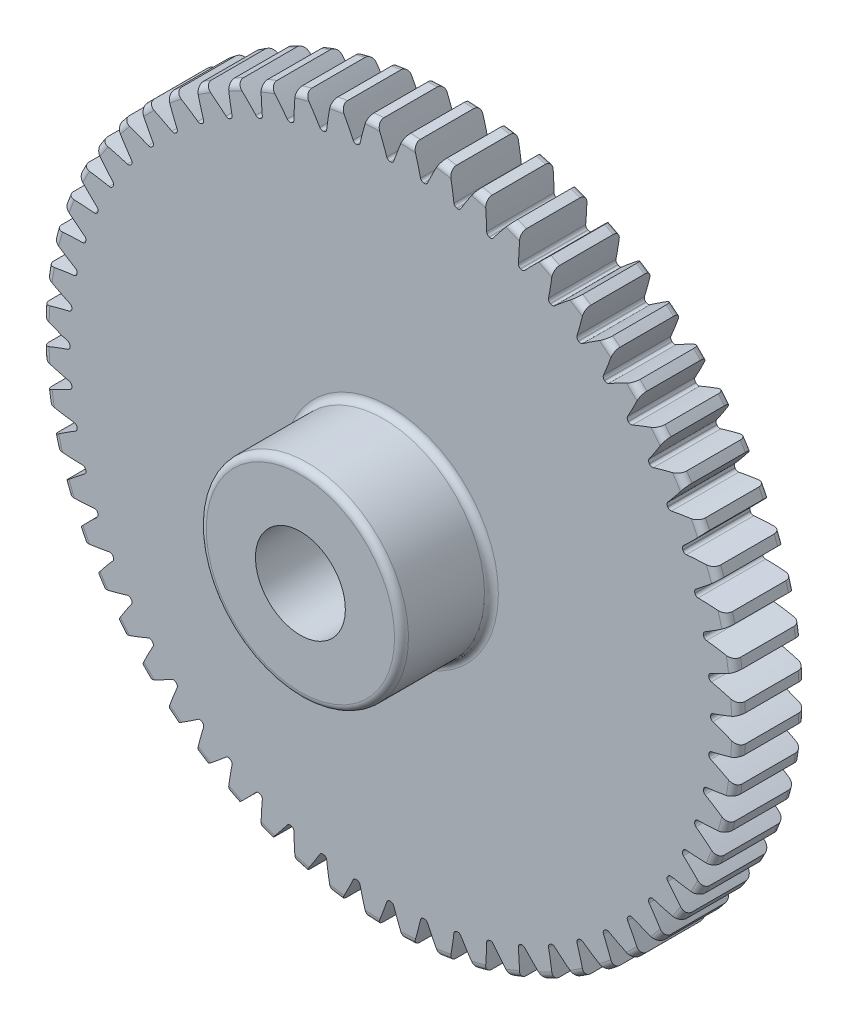
SolidWorks part; units mm, degrees
ref_plane "Front Plane" through (0, 0, 0) normal (0, 0, 1) x (1, 0, 0)
ref_plane "Top Plane" through (0, 0, 0) normal (0, 1, 0) x (1, 0, 0)
ref_plane "Right Plane" through (0, 0, 0) normal (1, 0, 0) x (0, 0, -1)
sketch "Sketch1" plane through (0, 0, 0) normal (0, 0, 1) x (1, 0, 0)
  line L0 (-762, 0) -> (762, 0) construction
  circle A0 centre (0, 0) radius 31 construction
  circle A1 centre (0, 0) radius 30 construction
  circle A2 centre (0, 0) radius 28.5 construction
  circle A3 centre (0, 0) radius 9 construction
  circle A4 centre (0, 0) radius 4 construction
  dimension "D2" = 1
  dimension "D3" = 2.5
  dimension "D1" = 2.5
sketch "Sketch2" plane through (0, 0, 0) normal (1, 0, 0) x (0, 0, -1)
  line L0 (0, 0) -> (-6, 0) construction
  line L1 (-6, 0) -> (-14, 0) construction
  dimension "Overall Width" = 14
  dimension "Face Width" = 6
sketch "Sketch4" plane through (0, 0, 0) normal (1, 0, 0) x (0, 0, -1)
  line L0 (-14, 4) -> (-14, 9)
  line L1 (-14, 9) -> (-6, 9)
  line L2 (-6, 9) -> (-6, 31)
  line L3 (-6, 31) -> (0, 31)
  line L4 (0, 31) -> (0, 4)
  line L5 (-6, 9) -> (-6, 0) construction
  line L6 (0, 31) -> (0, -31) construction
  line L7 (-6, 9) -> (0, 9) construction
  line L12 (-14, 4) -> (0, 4)
revolve "Revolve1" add sketch "Sketch4" angle 360 about L1
fillet "Fillet2" radius 0.62 4 edges at (0, 9, 14) (0, 9, 6) (0, 31, 6) (0, 31, 0)
sketch "Sketch7" plane through (0, 0, 6) normal (0, 0, 1) x (1, 0, 0)
  line L0 (0, 0) -> (0, 31) construction
  line L1 (0.7853, 29.9897) -> (1.1745, 30.9777) construction
  line L3 (1.6224, 30.9575) -> (1.5701, 29.9589) construction
  line L4 (1.5701, 29.9589) -> (1.4916, 28.4609) construction
  line L5 (0, 0) -> (1.4916, 28.4609) construction
  line L6 (0.7853, 29.9897) -> (0, 0) construction
  line L7 (0.7853, 29.9897) -> (0.8115, 30.9894) construction
  line L8 (0.7853, 29.9897) -> (0, 0) construction
  circle A0 centre (0, 0) radius 31 construction
  arc A1 (-0.0279, 28.5) -> (0.0279, 28.5) centre (0, 0) cw
  circle A2 centre (0, 0) radius 28.5 construction
  arc A3 (-0.7853, 29.9897) -> (0.7853, 29.9897) centre (0, 0) cw construction
  circle A4 centre (0, 0) radius 30 construction
  arc A5 (2.0499, 30.9322) -> (1.1947, 30.977) centre (0, 0) ccw construction
  arc A6 (0.7853, 29.9897) -> (2.3538, 29.9075) centre (0, 0) cw construction
  arc A7 (-1.1947, 30.977) -> (1.1947, 30.977) centre (0, 0) cw
  arc A8 (0.3121, 28.7029) -> (1.1947, 30.977) centre (28.6978, 18.9947) cw
  arc A9 (-0.3121, 28.7029) -> (-1.1947, 30.977) centre (-28.6978, 18.9947) ccw
  arc A10 (-0.0279, 28.5) -> (-0.3121, 28.7029) centre (-0.0282, 28.8) cw
  arc A11 (0.0279, 28.5) -> (0.3121, 28.7029) centre (0.0282, 28.8) ccw
  point P26 (-0.2432, 28.499)
  point P29 (0.2432, 28.499)
  dimension "D4" = 0.3
  dimension "D5" = 30
  dimension "D3" = 20
  dimension "D1" = 3.1416
  dimension "D2" = 1.5708
extrude "Cut-Extrude2" cut sketch "Sketch7" against normal through all
pattern_circular "CirPattern1" count 60 over 360 about axis through (0, 0, 14) along (0, 0, -1) of "Cut-Extrude2"
equation "\"D1@Sketch1\"=2.5*(\"Pitch Dia.@Sketch1\"/\"Number of Teeth@Sketch1\")"
equation "\"D1@CirPattern1\"=\"Number of Teeth@Sketch1\""
equation "\"D1@Fillet2\"=\"OD@Sketch1\"*.01"
equation "\"D1@Sketch7\"=3.14159*(\"Pitch Dia.@Sketch1\"/\"Number of Teeth@Sketch1\")"
equation "\"D2@Sketch7\"=\"D1@Sketch7\"/2"
equation "\"D4@Sketch7\"=\"D1@Sketch7\"*.0955"
equation "\"D5@Sketch7\"=\"Pitch Dia.@Sketch1\"/2"
